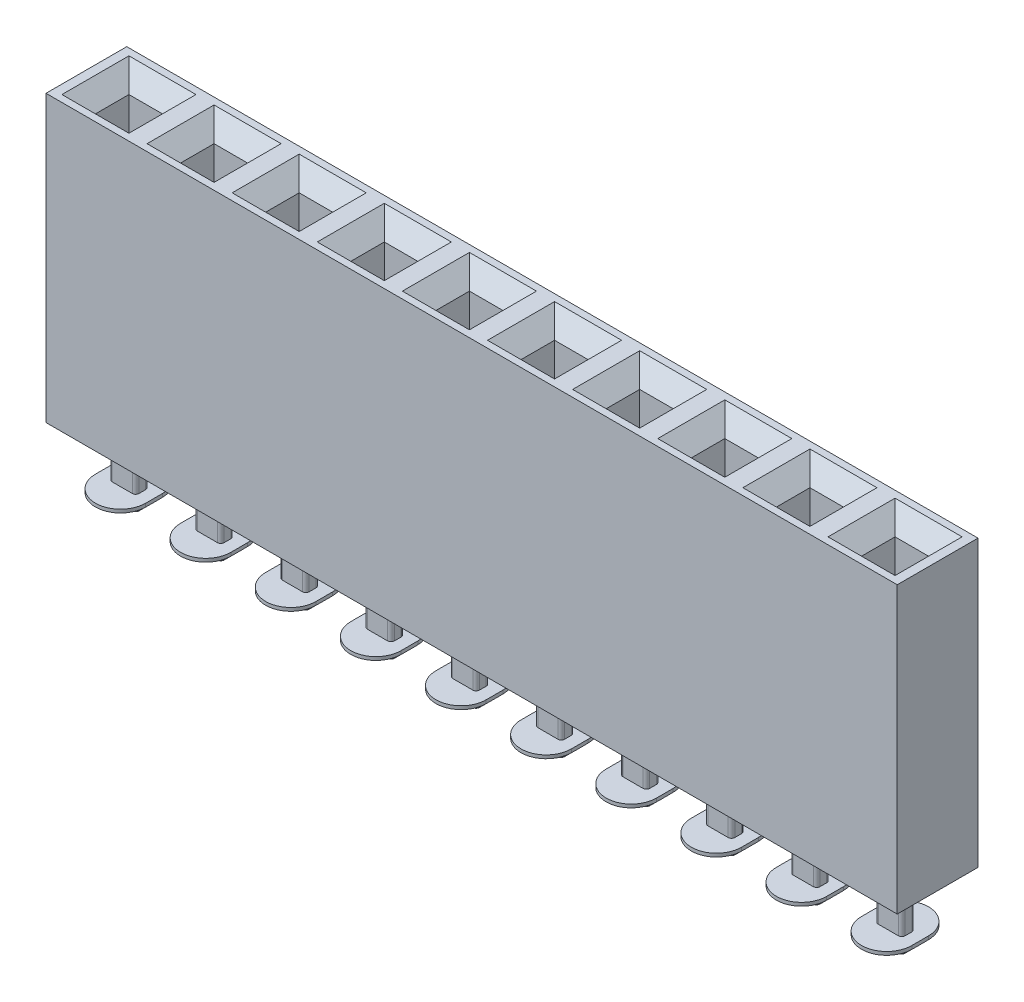
SolidWorks part; units mm, degrees
material "PA Type 6"
ref_plane "Front Plane" through (0, 0, 0) normal (0, 0, 1) x (1, 0, 0)
ref_plane "Top Plane" through (0, 0, 0) normal (0, 1, 0) x (1, 0, 0)
ref_plane "Right Plane" through (0, 0, 0) normal (1, 0, 0) x (0, 0, -1)
ref_plane "Plane1" through (0, -1.65, 0) normal (0, 1, 0) x (1, 0, 0)
sketch "Sketch2" plane through (0, 0, 0) normal (0, 1, 0) x (1, 0, 0)
  line L0 (0, -55) -> (0, 55) construction
  line L1 (-1.27, 1.205) -> (24.13, 1.205)
  line L2 (-1.27, 1.205) -> (-1.27, -1.205)
  line L3 (-1.27, -1.205) -> (24.13, -1.205)
  line L4 (24.13, 1.205) -> (24.13, -1.205)
  line L5 (-55, 0) -> (55, 0) construction
  dimension "D1" = 25.4
  dimension "D2" = 1.27
  dimension "D3" = 2.41
  dimension "D4" = 1.205
extrude "Boss-Extrude1" add sketch "Sketch2" along normal blind 8.51
sketch "Sketch5" plane through (0, 8.51, 0) normal (0, 1, 0) x (1, 0, 0)
  line L0 (-4.6805, 0) -> (4.6805, 0) construction
  line L1 (0.5, 0.5) -> (-0.5, 0.5)
  line L2 (0.5, 0.5) -> (0.5, -0.5)
  line L3 (0.5, -0.5) -> (-0.5, -0.5)
  line L4 (-0.5, 0.5) -> (-0.5, -0.5)
  line L5 (0, -1.3255) -> (0, 1.3255) construction
  dimension "D1" = 0.5
  dimension "D2" = 1
  dimension "D3" = 0.5
extrude "Cut-Extrude1" cut sketch "Sketch5" against normal blind 5
chamfer "Chamfer1" distance 0.5 angle 45 4 edges at (-0.5, 8.51, 0) (0, 8.51, 0.5) (0.5, 8.51, 0) (0, 8.51, -0.5)
pattern_linear "LPattern3" count 10 spacing 2.54 along (1, 0, 0) of "Chamfer1", "Cut-Extrude1"
sketch "Sketch8" plane through (0, 0, 0) normal (0, 1, 0) x (1, 0, 0)
  line L0 (0, -1.3255) -> (0, 1.3255) construction
  line L1 (-0.3, -0.2) -> (0.3, -0.2)
  line L2 (-0.4, -0.1) -> (-0.4, 0.1)
  line L3 (-0.3, 0.2) -> (0.3, 0.2)
  line L4 (0.4, -0.1) -> (0.4, 0.1)
  line L5 (-4.6805, 0) -> (4.6805, 0) construction
  arc A0 (-0.3, -0.2) -> (-0.4, -0.1) centre (-0.3, -0.1) cw
  arc A1 (0.3, -0.2) -> (0.4, -0.1) centre (0.3, -0.1) ccw
  arc A2 (0.3, 0.2) -> (0.4, 0.1) centre (0.3, 0.1) cw
  arc A3 (-0.4, 0.1) -> (-0.3, 0.2) centre (-0.3, 0.1) cw
  point P10 (-0.4, -0.2)
  point P13 (0.4, -0.2)
  point P16 (0.4, 0.2)
  dimension "D5" = 0.1
  dimension "D1" = 0.4
  dimension "D2" = 0.8
  dimension "D3" = 0.4
  dimension "D4" = 0.2
extrude "Boss-Extrude2" add sketch "Sketch8" against normal blind 2 separate body
sketch "Sketch10" plane through (0, -1.65, 0) normal (0, 1, 0) x (1, 0, 0)
  line L0 (0, -0.25) -> (0, 0.25) construction
  line L1 (0, -1.3255) -> (0, 1.3255) construction
  line L2 (-0.75, -0.25) -> (-0.75, 0.25)
  line L3 (0.75, -0.25) -> (0.75, 0.25)
  line L4 (-5.7805, 0) -> (5.7805, 0) construction
  arc A0 (-0.75, -0.25) -> (0.75, -0.25) centre (0, -0.25) ccw
  arc A1 (0.75, 0.25) -> (-0.75, 0.25) centre (0, 0.25) ccw
  point P5 (0, 0)
  dimension "D1" = 1.5
  dimension "D2" = 0.5
extrude "Boss-Extrude3" add sketch "Sketch10" along normal blind 0.1
fillet "Fillet2" radius 0.4 6 edges at (-0.3707, -1.65, -0.1707) (-0.3707, -1.65, 0.1707) (0, -1.65, 0.2) (0.3707, -1.65, 0.1707) (0.3707, -1.65, -0.1707) (0, -1.65, -0.2)
pattern_linear "Répétition linéaire1" count 10 spacing 2.54 along (1, 0, 0) of bodies 105 104
ref_axis "Axis1" through (0, -2.5255, 0) along (0, 1, 0)
equation "\"D1@Sketch2\"=2.54 * 10"
